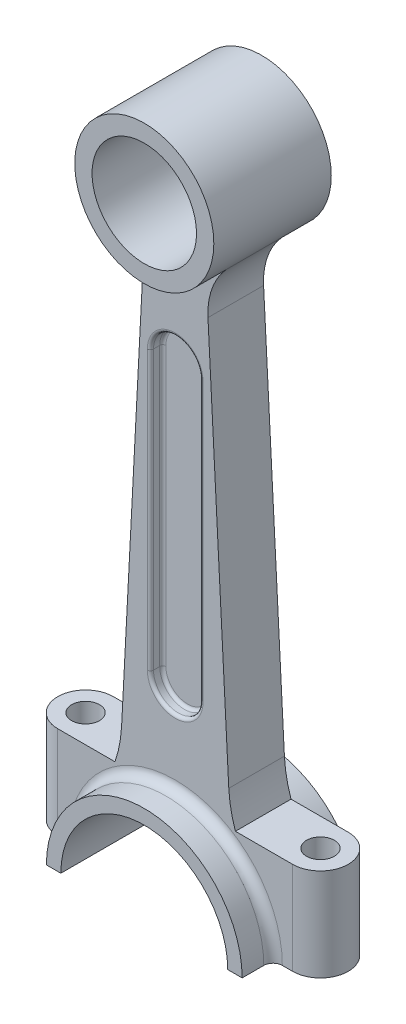
SolidWorks part; units mm, degrees
ref_plane "Front Plane" through (0, 0, 0) normal (0, 0, 1) x (1, 0, 0)
ref_plane "Top Plane" through (0, 0, 0) normal (0, 1, 0) x (1, 0, 0)
ref_plane "Right Plane" through (0, 0, 0) normal (1, 0, 0) x (0, 0, -1)
sketch "Sketch1" plane through (0, 0, 0) normal (0, 0, 1) x (1, 0, 0)
  line L0 (0, 0) -> (0, -201.2) construction
  line L1 (-18.127, -175.2281) -> (-10, -20.1556)
  line L2 (18.127, -175.2281) -> (10, -20.1556)
  line L3 (-31.6722, -201.2) -> (31.6722, -201.2) construction
  line L4 (-31.6722, -201.2) -> (-27, -201.2)
  line L5 (27, -201.2) -> (31.6722, -201.2)
  circle A0 centre (0, 0) radius 22.5
  circle A1 centre (0, 0) radius 16.9
  arc A2 (27, -201.2) -> (-27, -201.2) centre (0, -201.2) ccw
  arc A3 (31.6722, -201.2) -> (-31.6722, -201.2) centre (0, -201.2) ccw
  dimension "D1" = 45
  dimension "D2" = 33.8
  dimension "D3" = 201.2
  dimension "D4" = 20
  dimension "D5" = 6
extrude "Boss-Extrude1" add sketch "Sketch1" along normal mid plane 38 contours A1 A0 | A3 A2 region at (0, -170.236, 0) region at (-11.5231, 18.5805, 0)
extrude "Boss-Extrude2" add sketch "Sketch1<3>" along normal mid plane 18 contours A0 L0 A3 L2 | L0 A0 L1 A3 region at (0, -103.5216, 0)
sketch "Sketch1<3>" plane through (0, 0, 0) normal (0, 0, 1) x (1, 0, 0) same geometry as "Sketch1"
sketch "Sketch2" plane through (0, 0, 9) normal (0, 0, 1) x (1, 0, 0)
  line L0 (0, 0) -> (0, -190.569) construction
  line L1 (0, -50.2845) -> (0, -140.2845) construction
  line L2 (8, -50.2845) -> (8, -140.2845)
  line L3 (-8, -50.2845) -> (-8, -140.2845)
  arc A0 (8, -50.2845) -> (-8, -50.2845) centre (0, -50.2845) ccw
  arc A1 (-8, -140.2845) -> (8, -140.2845) centre (0, -140.2845) ccw
  point P5 (0, -95.2845)
  dimension "D1" = 8
  dimension "D2" = 90
extrude "Cut-Extrude1" cut sketch "Sketch2" against normal blind 4
mirror "Mirror1" about plane through (0, 0, 0) normal (0, 0, 1) of "Cut-Extrude1"
fillet "Fillet1" radius 1 8 edges at (0, -148.2845, 9) (-8, -95.2845, 9) (0, -42.2845, 9) (0, -148.2845, 5) (-8, -95.2845, 5) (0, -42.2845, 5) (8, -95.2845, 5) (8, -95.2845, 9)
fillet "Fillet2" radius 1 8 edges at (-8, -95.2845, -9) (0, -42.2845, -9) (8, -95.2845, -9) (0, -148.2845, -9) (-8, -95.2845, -5) (0, -148.2845, -5) (8, -95.2845, -5) (0, -42.2845, -5)
fillet "Fillet3" radius 40 2 edges at (-18.127, -175.2281, 0) (18.127, -175.2281, 0)
fillet "Fillet5" radius 22.5 2 edges at (-10, -20.1556, 0) (10, -20.1556, 0)
ref_plane "Plane1" through (0, -171.2, 0) normal (0, -1, 0) x (-1, 0, 0)
sketch "Sketch3" plane through (0, -171.2, 0) normal (0, -1, 0) x (-1, 0, 0)
  line L0 (38, 0) -> (-38, 0) construction
  line L1 (38, -9) -> (-38, -9)
  line L2 (38, 9) -> (-38, 9)
  arc A0 (38, -9) -> (38, 9) centre (38, 0) ccw
  arc A1 (-38, 9) -> (-38, -9) centre (-38, 0) ccw
  point P2 (0, 0)
  dimension "D2" = 9
  dimension "D1" = 76
extrude "Boss-Extrude3" add sketch "Sketch3" along normal up to surface (30 mm away) up to face at (-29.3361, -201.2, 0)
sketch "Sketch4" plane through (0, 0, 9) normal (0, 0, 1) x (1, 0, 0)
  line L1 (-27, -201.2) -> (27, -201.2)
  line L2 (-27, -201.2) -> (27, -201.2)
  arc A1 (27, -201.2) -> (-27, -201.2) centre (0, -201.2) ccw
  arc A2 (27, -201.2) -> (-27, -201.2) centre (0, -201.2) ccw
  dimension "D1" = 0
extrude "Cut-Extrude2" cut sketch "Sketch4" against normal through all
sketch "Sketch5" plane through (0, -171.2, 0) normal (0, 1, 0) x (1, 0, 0)
  circle A0 centre (-38, 0) radius 4.5
  circle A1 centre (38, 0) radius 4.5
  dimension "D1" = 9
  dimension "D2" = 9
extrude "Cut-Extrude3" cut sketch "Sketch5" against normal through all
fillet "Fillet6" radius 3 2 edges at (0, -169.5278, 9) (0, -169.5278, -9)
